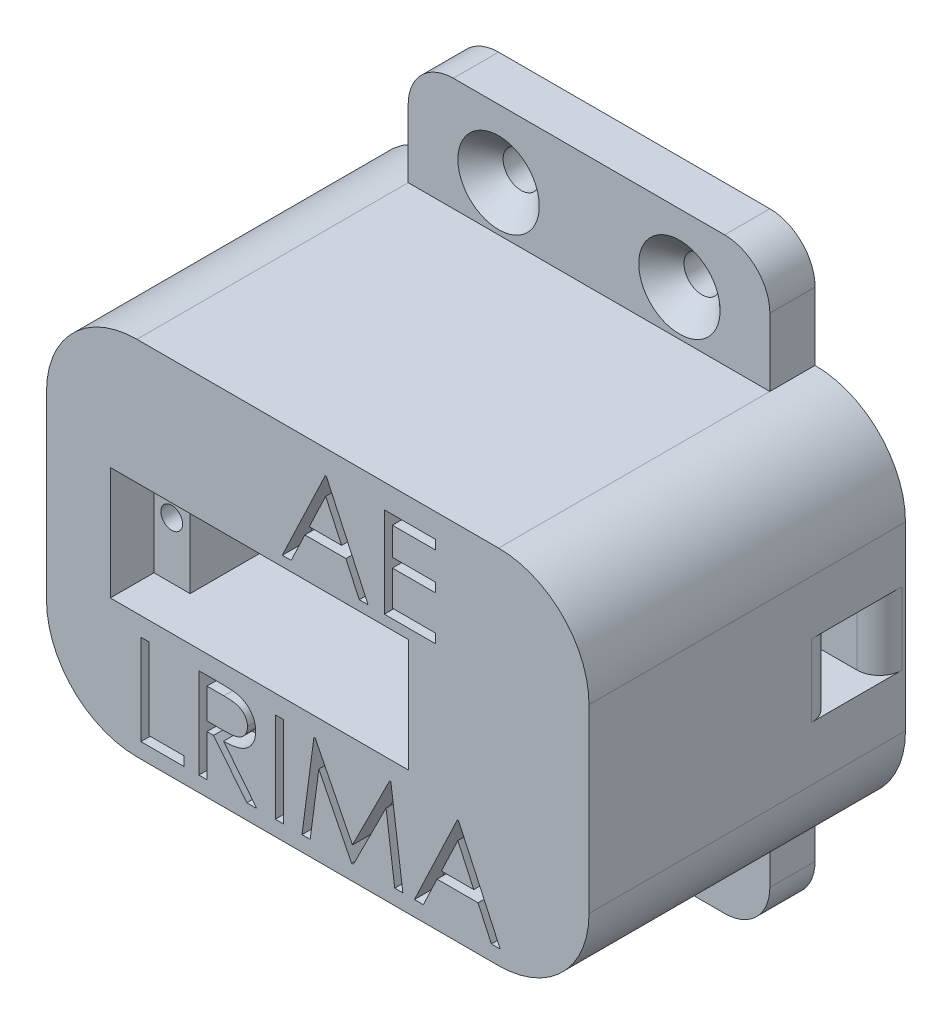
SolidWorks part; units mm, degrees
ref_plane "Plan de face" through (0, 0, 0) normal (0, 0, 1) x (1, 0, 0)
ref_plane "Plan de dessus" through (0, 0, 0) normal (0, 1, 0) x (1, 0, 0)
ref_plane "Plan de droite" through (0, 0, 0) normal (1, 0, 0) x (0, 0, -1)
sketch "Esquisse1" plane through (0, 0, 0) normal (0, 0, 1) x (1, 0, 0)
  line L0 (-30, 0) -> (30, 0)
  line L5 (30, 0) -> (30, 40)
  line L6 (-30, 0) -> (-30, 40)
  line L7 (-30, 40) -> (30, 40)
  point P7 (0, 0)
extrude "Boss.-Extru.1" add sketch "Esquisse1" along normal blind 35
sketch "Esquisse2" plane through (0, 0, 0) normal (0, -1, 0) x (1, 0, 0)
  line L0 (0, 2.8693) -> (0, 35)
  line L1 (-17.9445, 2.8693) -> (5.0555, 2.8693)
  line L2 (-30, 35) -> (30, 35) construction
  line L3 (5.0555, 2.8693) -> (5.0555, 19.1193)
  line L4 (-30, 35) -> (-30, 0) construction
  line L5 (-30, 17.5) -> (30, 17.5)
  line L6 (30, 35) -> (30, 0) construction
  line L7 (5.0555, 19.1193) -> (-17.9445, 19.1193)
  line L8 (-17.9445, 19.1193) -> (-17.9445, 2.8693)
  line L9 (-22.9445, 19.1193) -> (10.0555, 19.1193)
  line L10 (-22.9445, 19.1193) -> (-22.9445, 35)
  line L11 (-22.9445, 35) -> (10.0555, 35)
  line L12 (10.0555, 35) -> (10.0555, 19.1193)
  line L13 (-22.9445, 35) -> (-22.9445, 30.1738)
  line L14 (-22.9445, 30.1738) -> (-18.9445, 30.1738)
  line L15 (-18.9445, 30.1738) -> (-18.9445, 19.1193)
  line L16 (10.0555, 30.1738) -> (7.0555, 30.1738)
  line L17 (7.0555, 30.1738) -> (7.0555, 19.1193)
  point P3 (0, 18.9347)
  point P12 (-6.4445, 2.8693)
  point P17 (-6.4445, 19.1193)
extrude "Enlèv. mat.-Extru.1" cut sketch "Esquisse2" against normal mid plane 12.5 from offset 20 contours L10 L9 L7 L0 L4 | L12 L4 L0 L7 L9 | L5 L8 L1 L0 | L5 L0 L1 L3 region at (-8.9722, 0, 10.1847) region at (2.5278, 0, 10.1847) region at (-10.164, 0, 27.3929) region at (4.1031, 0, 27.6922) offset against normal yes
sketch "Esquisse3" plane through (0, 40, 0) normal (0, 1, 0) x (1, 0, 0)
  line L0 (-17.9445, -17.5) -> (-17.9445, -19.1193)
  line L1 (-17.9445, -17.5) -> (5.0555, -17.5) construction
  line L2 (-17.9445, -17.5) -> (-17.9445, -2.8693) construction
  line L3 (-18.9445, -19.1193) -> (7.0555, -19.1193) construction
  line L4 (-17.9445, -19.1193) -> (5.0555, -19.1193)
  line L5 (5.0555, -19.1193) -> (5.0555, -17.5)
  line L6 (5.0555, -17.5) -> (-17.9445, -17.5)
extrude "Enlèv. mat.-Extru.2" cut sketch "Esquisse3" against normal mid plane 12.5 from offset 20 contours L6 L0 L4 L5 offset against normal yes
fillet "Congé1" radius 10 4 edges at (-30, 0, 17.5) (30, 0, 17.5) (30, 40, 17.5) (-30, 40, 17.5)
sketch "Esquisse4" plane through (0, 0, 0) normal (0, -1, 0) x (1, 0, 0)
  line L0 (-20, 0) -> (20, 0)
  line L6 (-20, 5) -> (20, 5)
  line L7 (20, 5) -> (20, 0)
  line L8 (-20, 5) -> (-20, 0)
fillet "Congé2" radius 2.5 2 edges at (5.0555, 20, 19.1193) (-17.9445, 20, 19.1193)
extrude "Boss.-Extru.2" add sketch "Esquisse4" along normal blind 12.5 separate body
sketch "Esquisse5" plane through (0, 40, 0) normal (0, 1, 0) x (1, 0, 0)
  line L0 (-20, 0) -> (-20, -5)
  line L1 (-20, 0) -> (-20, -35) construction
  line L2 (-20, -5) -> (20, -5)
  line L3 (20, -35) -> (20, 0) construction
  line L4 (20, -5) -> (20, 0)
  line L5 (20, 0) -> (-20, 0)
extrude "Boss.-Extru.3" add sketch "Esquisse5" along normal blind 12.5
fillet "Congé3" radius 5 2 edges at (-20, 52.5, 2.5) (20, 52.5, 2.5)
fillet "Congé4" radius 5 2 edges at (20, -12.5, 2.5) (-20, -12.5, 2.5)
sketch "Esquisse6" plane through (0, 0, 5) normal (0, 0, 1) x (1, 0, 0)
  circle A1 centre (-10, -5) radius 2
  circle A2 centre (10, -5) radius 2
  circle A3 centre (10, 45) radius 2
  circle A4 centre (-10, 45) radius 2
  point P2 (0, 0)
extrude "Enlèv. mat.-Extru.3" cut sketch "Esquisse6" against normal mid plane 12.5
chamfer "Chanfrein1" distance 2.5 angle 45 2 edges at (8, -5, 5) (-12, -5, 5)
chamfer "Chanfrein2" distance 2.5 angle 45 2 edges at (8, 45, 5) (-12, 45, 5)
sketch "Esquisse7" plane through (0, 0, 35) normal (0, 0, 1) x (1, 0, 0)
  text T0 "LRIMA" font "Century Gothic" height 10
extrude "Enlèv. mat.-Extru.4" cut sketch "Esquisse7" against normal blind 2.5
sketch "Esquisse8" plane through (0, 0, 35) normal (0, 0, 1) x (1, 0, 0)
  text T0 "AE" font "Century Gothic" height 10
extrude "Enlèv. mat.-Extru.5" cut sketch "Esquisse8" against normal blind 2.5
sketch "Esquisse9" plane through (0, 0, 19.1193) normal (0, 0, 1) x (1, 0, 0)
  line L0 (-17.9445, 20) -> (-19.7779, 20)
  line L1 (-17.9445, 26.25) -> (-17.9445, 13.75) construction
  line L4 (-19.7779, 20) -> (-17.9445, 20)
  line L6 (-22.9445, 26.25) -> (10.0555, 26.25)
  line L7 (10.0555, 26.25) -> (-6.4445, 26.25)
  line L8 (-6.4445, 26.25) -> (-6.4445, 13.75)
  line L9 (10.0555, 13.75) -> (-22.9445, 13.75) construction
  circle A0 centre (-20.9779, 20) radius 1.2
  circle A1 centre (8.089, 20) radius 1.2
extrude "Enlèv. mat.-Extru.6" cut sketch "Esquisse9" along normal blind 20 contours A0 | A1
sketch "Esquisse11" plane through (5.0555, 0, 0) normal (-1, 0, 0) x (0, 0, 1)
  line L1 (2.8693, 26.25) -> (2.8693, 13.75) construction
  line L2 (7.8693, 16) -> (7.8693, 24)
  line L3 (7.8693, 24) -> (2.8693, 24)
  line L4 (2.8693, 24) -> (2.8693, 16)
  line L5 (2.8693, 16) -> (7.8693, 16)
  point P7 (7.8693, 20)
extrude "Enlèv. mat.-Extru.7" cut sketch "Esquisse11" against normal blind 40
fillet "Congé5" radius 2.5 2 edges at (30, 20, 7.8693) (30, 20, 2.8693)
fillet "Congé6" radius 2.5 2 edges at (5.0555, 16, 5.3693) (5.0555, 24, 5.3693)
